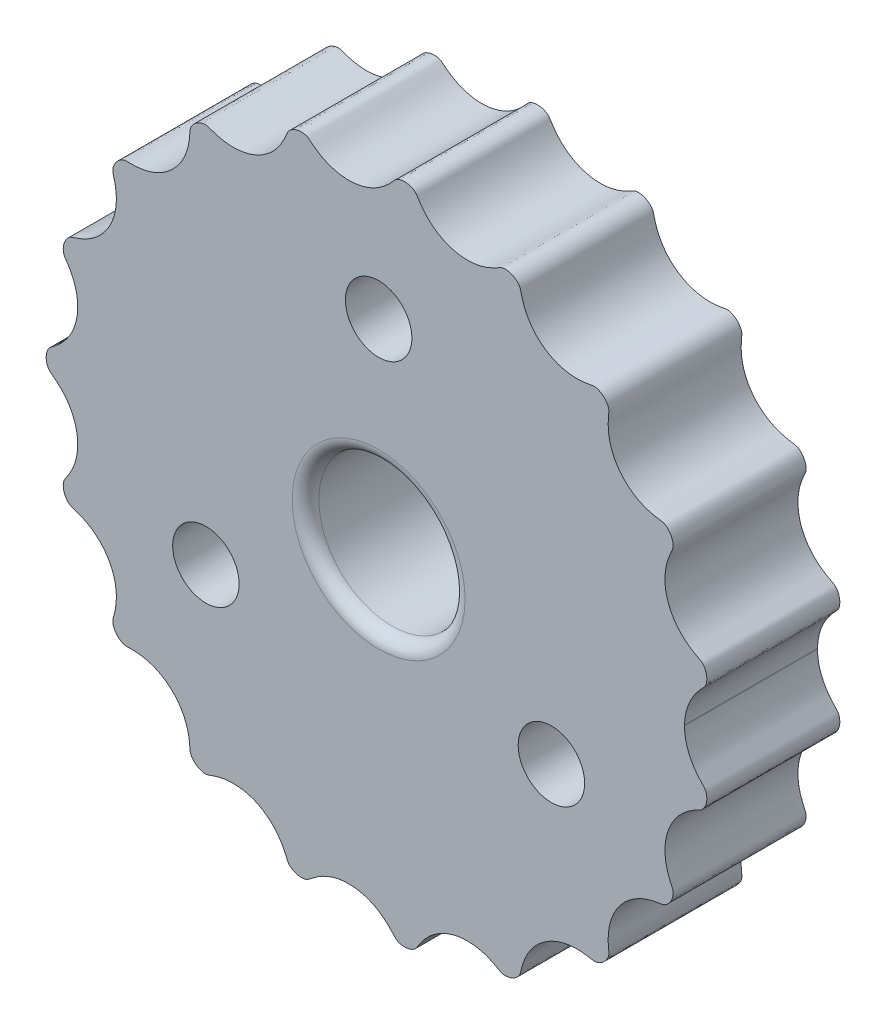
SolidWorks part; units mm, degrees
ref_plane "Ebene vorne" through (0, 0, 0) normal (0, 0, 1) x (1, 0, 0)
ref_plane "Ebene oben" through (0, 0, 0) normal (0, 1, 0) x (1, 0, 0)
ref_plane "Ebene rechts" through (0, 0, 0) normal (1, 0, 0) x (0, 0, -1)
sketch "Skizze1" plane through (0, 0, 0) normal (0, 0, 1) x (1, 0, 0)
  circle A0 centre (0, 0) radius 25
  dimension "D1" = 50
extrude "Aufsatz-Linear austragen1" add sketch "Skizze1" along normal blind 10 contours A0
sketch "Skizze3" plane through (0, 0, 10) normal (0, 0, 1) x (1, 0, 0)
  circle A0 centre (0, 25) radius 0.5
  circle A1 centre (0, 0) radius 25 construction
extrude "Schnitt-Linear austragen1" cut sketch "Skizze3" against normal up to next contours A0
pattern_circular "Kreismuster3" [suppressed] count 30 over 360 of bodies 102
sketch "Skizze9" plane through (0, 0, 10) normal (0, 0, 1) x (1, 0, 0)
  line L0 (23.0004, 0.0609) -> (23, 0)
  spline S0 degree 4 poles (21.8349, 10.4363) (21.7595, 10.2402) (21.6296, 9.8393) (21.51, 9.2154) (21.5169, 8.368) (21.6949, 7.529) (21.9996, 6.8362) (22.3616, 6.2918) (22.7278, 5.8789) (23.0126, 5.6175) (23.2743, 5.4145) (23.4929, 5.2661) (23.6607, 5.1622) (23.8217, 5.0701) (23.9556, 4.9977) (24.0711, 4.9376) (24.1728, 4.8842) (24.259, 4.8347) (24.3648, 4.7517) (24.4596, 4.6337) (24.5411, 4.4963) (24.6203, 4.3033) (24.6742, 4.0826) (24.6893, 3.8352) (24.654, 3.6047) (24.5939, 3.4337) (24.5231, 3.3149) (24.4482, 3.2274) (24.3391, 3.1139) (24.2149, 2.9815) (24.0838, 2.8346) (23.9185, 2.6346) (23.746, 2.4006) (23.5642, 2.1174) (23.3859, 1.7712) (23.2392, 1.419) (23.1381, 1.082) (23.0724, 0.8012) (23.0325, 0.5259) (23.0102, 0.3454) (22.9992, 0.0775) (22.999, -0.0665) (23.009, -0.3222) (23.0286, -0.4951) (23.0652, -0.7605) (23.1283, -1.0483) (23.2566, -1.484) (23.4559, -1.9318) (23.6809, -2.3132) (23.9099, -2.6224) (24.0743, -2.8241) (24.2067, -2.9723) (24.3336, -3.1084) (24.4467, -3.2256) (24.524, -3.3159) (24.583, -3.4156) (24.6246, -3.5208) (24.6638, -3.6686) (24.6852, -3.8609) (24.6735, -4.0869) (24.6205, -4.3068) (24.5464, -4.4848) (24.4695, -4.6144) (24.4037, -4.7024) (24.3311, -4.7784) (24.2516, -4.8395) (24.1377, -4.9039) (24.0001, -4.974) (23.846, -5.0565) (23.6352, -5.1762) (23.3933, -5.3292) (23.1212, -5.5276) (22.8316, -5.7799) (22.5655, -6.0569) (22.2617, -6.4361) (21.9548, -6.9332) (21.7249, -7.4811) (21.5829, -8.0653) (21.5273, -8.5636) (21.5216, -8.9708) (21.5541, -9.3694) (21.6218, -9.7561) (21.7087, -10.0818) (21.7995, -10.3483) (21.8842, -10.5632) (21.9558, -10.729) (22.0248, -10.8829) (22.0924, -11.0248) (22.1404, -11.1746) (22.1504, -11.3468) (22.1274, -11.5442) (22.061, -11.7619) (21.9505, -11.9788) (21.8083, -12.1674) (21.6614, -12.3022) (21.5247, -12.3914) (21.414, -12.4372) (21.3301, -12.4586) (21.2321, -12.4761) (21.1212, -12.4922) (20.9921, -12.5121) (20.8374, -12.539) (20.6763, -12.5709) (20.4655, -12.6198) (20.1205, -12.7175) (19.6539, -12.8972) (19.0899, -13.2109) (18.4957, -13.6939) (17.9798, -14.3033) (17.5818, -15.0184) (17.3599, -15.7125) (17.2758, -16.2728) (17.2579, -16.6757) (17.2603, -16.9123) (17.2683, -17.0871) (17.2802, -17.2498) (17.2921, -17.3816) (17.3037, -17.4944) (17.3123, -17.5952) (17.3148, -17.684) (17.3037, -17.7848) (17.2728, -17.8946) (17.2143, -18.0352) (17.1157, -18.1992) (16.9706, -18.3697) (16.7741, -18.5306) (16.5633, -18.6445) (16.3771, -18.7041) (16.228, -18.7183) (16.1024, -18.7064) (15.9827, -18.6847) (15.837, -18.6581) (15.664, -18.6292) (15.4825, -18.6042) (15.2505, -18.5802) (14.9676, -18.5655) (14.5429, -18.5729) (14.0693, -18.6361) (13.6043, -18.7559) (13.0666, -18.9667) (12.6278, -19.2052) (12.2149, -19.5036) (11.8389, -19.8586) (11.5583, -20.1838) (11.3157, -20.5303) (11.1115, -20.893) (10.9662, -21.2192) (10.865, -21.4994) (10.7941, -21.7329) (10.7511, -21.8937) (10.717, -22.0322) (10.6867, -22.159) (10.6596, -22.2741) (10.6135, -22.4098) (10.5273, -22.5357) (10.4274, -22.6442) (10.2911, -22.7583) (10.1265, -22.8625) (9.947, -22.94) (9.7581, -22.9885) (9.581, -23.009) (9.446, -23.0074) (9.3222, -22.9883) (9.215, -22.9494) (9.1367, -22.9105) (9.0374, -22.8556) (8.9163, -22.7867) (8.7704, -22.7082) (8.5994, -22.6214) (8.2969, -22.4821) (7.9364, -22.3488) (7.5146, -22.2402) (7.0313, -22.1759) (6.6328, -22.1607) (6.2298, -22.1836) (5.826, -22.2463) (5.4253, -22.3496) (5.032, -22.4941) (4.6565, -22.6767) (4.3023, -22.8948) (3.9755, -23.1429) (3.6777, -23.4168) (3.4441, -23.6748) (3.264, -23.904) (3.127, -24.0974) (3.026, -24.2496) (2.9434, -24.3794) (2.8771, -24.486) (2.8107, -24.5788) (2.7442, -24.6523) (2.6543, -24.7214) (2.5172, -24.8007) (2.3431, -24.8698) (2.129, -24.9172) (1.9104, -24.9257) (1.7254, -24.9049) (1.5597, -24.8634) (1.4272, -24.8123) (1.3018, -24.7374) (1.1919, -24.6254) (1.0929, -24.5126) (0.9862, -24.3949) (0.8714, -24.2728) (0.7167, -24.1173) (0.5166, -23.934) (0.1944, -23.6752) (-0.2816, -23.3734) (-0.8873, -23.1037) (-1.633, -22.9219) (-2.4119, -22.88) (-3.1838, -22.9833) (-3.829, -23.1953) (-4.2989, -23.431) (-4.6166, -23.6302) (-4.8236, -23.7746) (-4.9777, -23.8915) (-5.1193, -24.0037) (-5.2422, -24.1039) (-5.3368, -24.1704) (-5.4383, -24.2183) (-5.5428, -24.2496) (-5.6869, -24.2756) (-5.8715, -24.2822) (-6.0864, -24.2562) (-6.2931, -24.1927) (-6.4597, -24.1129) (-6.6006, -24.0204) (-6.7112, -23.9272) (-6.7966, -23.8241) (-6.8508, -23.7158) (-6.8984, -23.6058) (-6.9474, -23.4882) (-7.0086, -23.3469) (-7.0843, -23.183) (-7.1853, -22.982) (-7.3178, -22.7471) (-7.4915, -22.481) (-7.7159, -22.1922) (-7.9683, -21.919) (-8.2484, -21.6651) (-8.561, -21.4293) (-9, -21.1594) (-9.4852, -20.944) (-10.0058, -20.7949) (-10.5401, -20.7187) (-10.9664, -20.7017) (-11.386, -20.7263) (-11.7441, -20.7819) (-12.0407, -20.8508) (-12.2801, -20.9199) (-12.4645, -20.9804) (-12.619, -21.0347) (-12.7443, -21.0813) (-12.8432, -21.1127) (-12.9148, -21.1293) (-13.0155, -21.1409) (-13.1607, -21.1341) (-13.3458, -21.0947) (-13.5626, -21.0052) (-13.7727, -20.87) (-13.9463, -20.7079) (-14.067, -20.5439) (-14.1433, -20.3907) (-14.1772, -20.2506) (-14.1869, -20.1194) (-14.1984, -19.9464) (-14.2135, -19.7574) (-14.2357, -19.56) (-14.2744, -19.3096) (-14.3484, -18.9507) (-14.4988, -18.4602) (-14.7821, -17.8614) (-15.2347, -17.2299) (-15.8123, -16.6797) (-16.4915, -16.2457) (-17.1512, -15.9856) (-17.6884, -15.8653) (-18.0779, -15.8187) (-18.3444, -15.8008) (-18.5515, -15.7964) (-18.7472, -15.7971) (-18.9192, -15.8013) (-19.043, -15.798) (-19.1585, -15.7742) (-19.2639, -15.7342) (-19.3981, -15.6643) (-19.5524, -15.5524) (-19.7098, -15.3942) (-19.8355, -15.2104) (-19.9175, -15.0392) (-19.9694, -14.8748) (-19.9942, -14.7409) (-19.9941, -14.6091) (-19.9622, -14.4594) (-19.9209, -14.3132) (-19.8775, -14.147) (-19.8227, -13.9154) (-19.7703, -13.6388) (-19.7298, -13.3095) (-19.7155, -12.9316) (-19.7343, -12.5536) (-19.7865, -12.1771) (-19.8725, -11.8051) (-20.0235, -11.3478) (-20.2355, -10.9007) (-20.5061, -10.4779) (-20.8313, -10.0898) (-21.1296, -9.7984) (-21.4493, -9.5419) (-21.7859, -9.3207) (-22.0908, -9.1576) (-22.3541, -9.0395) (-22.5745, -8.9534) (-22.7489, -8.8919) (-22.9125, -8.8369) (-23.0664, -8.7897) (-23.2127, -8.7239) (-23.3488, -8.6133) (-23.48, -8.461) (-23.5959, -8.2631) (-23.6806, -8.0335) (-23.7223, -7.802) (-23.7216, -7.6015) (-23.6936, -7.4372) (-23.6459, -7.3113) (-23.587, -7.2131) (-23.5046, -7.0919) (-23.4135, -6.9559) (-23.317, -6.8055) (-23.1954, -6.601) (-23.0687, -6.3633) (-22.9383, -6.0757) (-22.7839, -5.6451) (-22.656, -5.1008) (-22.5992, -4.4221) (-22.6826, -3.6209) (-22.9272, -2.8308) (-23.2818, -2.1836) (-23.6363, -1.7308) (-23.9221, -1.4366) (-24.1011, -1.2722) (-24.239, -1.1546) (-24.372, -1.0482) (-24.4823, -0.963) (-24.578, -0.8915) (-24.662, -0.827) (-24.7323, -0.7672) (-24.8009, -0.6902) (-24.8613, -0.5932) (-24.925, -0.4573) (-24.9789, -0.2784) (-25.008, -0.0615) (-24.998, 0.1569) (-24.9616, 0.3399) (-24.9066, 0.5001) (-24.8504, 0.6156) (-24.7832, 0.7138) (-24.7061, 0.7903) (-24.6412, 0.8433) (-24.5549, 0.909) (-24.4487, 0.9887) (-24.3242, 1.0855) (-24.1833, 1.2011) (-24.0105, 1.3531) (-23.8111, 1.5469) (-23.5946, 1.788) (-23.3715, 2.0829) (-23.1734, 2.3976) (-23.0026, 2.7303) (-22.8251, 3.1685) (-22.6969, 3.6432) (-22.6277, 4.1442) (-22.6242, 4.6617) (-22.6664, 5.0951) (-22.7519, 5.5174) (-22.8777, 5.9244) (-23.0193, 6.2625) (-23.1587, 6.5356) (-23.2844, 6.7524) (-23.3883, 6.9169) (-23.4888, 7.0702) (-23.5875, 7.2108) (-23.6712, 7.3568) (-23.7142, 7.5309) (-23.7261, 7.7309) (-23.6995, 7.9535) (-23.6303, 8.1831) (-23.5263, 8.3908) (-23.4082, 8.549) (-23.2912, 8.6625) (-23.187, 8.7339) (-23.0968, 8.7758) (-22.9816, 8.8159) (-22.8484, 8.8583) (-22.6971, 8.9097) (-22.4871, 8.9859) (-22.2435, 9.0865) (-21.9662, 9.221) (-21.6596, 9.4005) (-21.366, 9.6063) (-21.0151, 9.8992) (-20.6164, 10.3191) (-20.2771, 10.8105) (-20.0144, 11.3636) (-19.8542, 11.8663) (-19.7673, 12.2789) (-19.7222, 12.6923) (-19.7169, 13.1024) (-19.7451, 13.4552) (-19.7902, 13.7494) (-19.8394, 13.9878) (-19.8839, 14.1718) (-19.9244, 14.3263) (-19.9596, 14.452) (-19.9815, 14.5509) (-19.9911, 14.6219) (-19.9935, 14.7217) (-19.9742, 14.8643) (-19.9195, 15.0445) (-19.8125, 15.2522) (-19.6794, 15.4254) (-19.5437, 15.5557) (-19.4017, 15.6607) (-19.2787, 15.7293) (-19.1504, 15.7794) (-19.0246, 15.7985) (-18.927, 15.8005) (-18.8133, 15.7991) (-18.6836, 15.7969) (-18.532, 15.7969) (-18.3106, 15.8023) (-18.0413, 15.8209) (-17.7248, 15.8628) (-17.3647, 15.941) (-16.9178, 16.0786) (-16.3974, 16.3085) (-15.8239, 16.6734) (-15.2485, 17.213) (-14.783, 17.8542) (-14.4878, 18.4827) (-14.3351, 18.9986) (-14.2627, 19.3751) (-14.2269, 19.6306) (-14.2075, 19.8274) (-14.1936, 20.0116) (-14.184, 20.1733) (-14.1697, 20.2905) (-14.1362, 20.4005) (-14.0873, 20.5015) (-14.0059, 20.6294) (-13.8804, 20.7742) (-13.7077, 20.9182) (-13.5127, 21.0276) (-13.335, 21.0939) (-13.1647, 21.1311) (-13.0232, 21.1444) (-12.8817, 21.1276) (-12.7469, 21.0817) (-12.6315, 21.0398) (-12.5001, 20.993) (-12.3519, 20.9431) (-12.1413, 20.8781) (-11.8655, 20.8075) (-11.5389, 20.7468) (-11.1616, 20.7097) (-10.7833, 20.7056) (-10.3038, 20.7432) (-9.7354, 20.8584) (-9.1818, 21.0633) (-8.6608, 21.3563) (-8.2599, 21.6542) (-7.9581, 21.9276) (-7.6875, 22.2243) (-7.4782, 22.5013) (-7.318, 22.7492) (-7.2006, 22.9556) (-7.1162, 23.1178) (-7.0401, 23.2775) (-6.9792, 23.4143) (-6.929, 23.5322) (-6.8829, 23.6417) (-6.8396, 23.7425) (-6.7732, 23.8583) (-6.6528, 23.9827) (-6.4911, 24.0996) (-6.2848, 24.1982) (-6.0489, 24.2635) (-5.8125, 24.2858) (-5.6133, 24.2679) (-5.4554, 24.2266) (-5.3475, 24.1752) (-5.2756, 24.1275) (-5.1963, 24.0667) (-5.1084, 23.9955) (-5.0052, 23.9133) (-4.8796, 23.817) (-4.7458, 23.7196) (-4.5657, 23.5973) (-4.2579, 23.4095) (-3.8065, 23.1883) (-3.1897, 22.9875) (-2.4297, 22.8812) (-1.6328, 22.9188) (-0.8411, 23.1135) (-0.1854, 23.421) (0.2799, 23.7378) (0.5861, 23.9964) (0.7572, 24.1576) (0.8795, 24.2813) (0.9904, 24.3996) (1.0788, 24.4971) (1.1534, 24.5815) (1.2215, 24.6556) (1.2849, 24.7171) (1.366, 24.7765) (1.4665, 24.8274) (1.6073, 24.879) (1.7912, 24.9173) (2.0109, 24.9275) (2.2284, 24.8982) (2.4076, 24.8457) (2.5635, 24.7759) (2.6787, 24.7064) (2.7776, 24.6216) (2.853, 24.522) (2.9089, 24.4353) (2.9741, 24.3312) (3.0513, 24.2111) (3.1673, 24.0378) (3.3314, 23.8136) (3.5412, 23.5623) (3.803, 23.2967) (4.0867, 23.0548) (4.3911, 22.8375) (4.7145, 22.6472) (5.1434, 22.4443) (5.6099, 22.2897) (6.1032, 22.1928) (6.6136, 22.1597) (7.04, 22.1755) (7.456, 22.233) (7.8578, 22.329) (8.1935, 22.443) (8.4659, 22.558) (8.6842, 22.6634) (8.8514, 22.7516) (9.0063, 22.8365) (9.1484, 22.9196) (9.3008, 22.9869) (9.4518, 23.0083) (9.5997, 23.0081) (9.7768, 22.9846) (9.9657, 22.9334) (10.1449, 22.8528) (10.3091, 22.7455) (10.4441, 22.6278) (10.5341, 22.5264) (10.6032, 22.4212) (10.6459, 22.3149) (10.6698, 22.2304) (10.6965, 22.1196) (10.7284, 21.9833) (10.7696, 21.8219) (10.8224, 21.6365) (10.926, 21.3181) (11.074, 20.9612) (11.2824, 20.576) (11.5658, 20.1761) (11.8273, 19.8724) (12.1194, 19.5924) (12.4404, 19.3397) (12.8767, 19.0608) (13.3474, 18.8414) (13.8414, 18.6865) (14.3466, 18.5977) (14.6978, 18.5693) (14.9983, 18.5678) (15.2424, 18.5806) (15.4319, 18.5983) (15.6163, 18.622) (15.7956, 18.651) (15.9629, 18.6804) (16.1188, 18.7114) (16.2634, 18.7186) (16.3919, 18.6957) (16.5434, 18.6484) (16.7128, 18.5663) (16.8932, 18.44) (17.0477, 18.2836) (17.1576, 18.1324) (17.2387, 17.9815) (17.2904, 17.8485) (17.3189, 17.7045) (17.3093, 17.5471) (17.2934, 17.3968) (17.2791, 17.2377) (17.2672, 17.07) (17.2581, 16.8499) (17.2594, 16.5774) (17.2886, 16.1632) (17.3914, 15.6061) (17.6071, 14.9758) (17.9828, 14.3047) (18.4824, 13.7066) (19.0811, 13.2137) (19.6713, 12.887) (20.16, 12.7034) (20.5195, 12.6059) (20.7644, 12.5521) (20.9536, 12.5182) (21.1309, 12.4903) (21.2868, 12.4679) (21.399, 12.4432) (21.5025, 12.4008) (21.5963, 12.345) (21.7134, 12.2561) (21.8437, 12.1238) (21.9702, 11.9469) (22.0634, 11.7504) (22.117, 11.5726) (22.1436, 11.4054) (22.149, 11.2598) (22.129, 11.1267) (22.0845, 11.0132) (22.035, 10.903) (21.9816, 10.7867) (21.919, 10.6454) (21.8499, 10.4782) (21.7706, 10.2666) (21.6878, 10.0086) (21.6103, 9.6986) (21.5509, 9.3355) (21.5224, 8.9626) (21.5272, 8.5827) (21.5787, 8.0866) (21.6972, 7.5846) (21.8865, 7.0905) (22.1457, 6.6199) (22.3909, 6.2662) (22.6666, 5.9438) (22.9679, 5.6541) (23.2503, 5.43) (23.5008, 5.2597) (23.7129, 5.1314) (23.8814, 5.0373) (24.0251, 4.9609) (24.1437, 4.9005) (24.2332, 4.8492) (24.2935, 4.8079) (24.37, 4.7415) (24.4633, 4.6297) (24.5599, 4.466) (24.6407, 4.2447) (24.683, 3.9972) (24.6804, 3.7586) (24.6403, 3.558) (24.5776, 3.3979) (24.4956, 3.2786) (24.4048, 3.1827) (24.2851, 3.0565) (24.1558, 2.9165) (24.0253, 2.7659) (23.8669, 2.5657) (23.6527, 2.2673) (23.442, 1.9019) (23.2546, 1.4742) (23.132, 1.0608) (23.0706, 0.7861) (23.0335, 0.5349) (23.0132, 0.3678) (23.0003, 0.1223) (22.9986, -0.0189) (23.0056, -0.2852) (23.0253, -0.4661) (23.0615, -0.7427) (23.1239, -1.029) (23.2494, -1.4644) (23.4447, -1.9094) (23.6681, -2.2941) (23.8991, -2.6086) (24.0657, -2.8141) (24.1984, -2.9632) (24.3246, -3.0987) (24.4356, -3.2143) (24.5132, -3.3018) (24.5877, -3.4196) (24.6374, -3.5547) (24.6701, -3.7073) (24.6838, -3.9154) (24.6644, -4.1417) (24.6, -4.381) (24.4916, -4.5912) (24.3759, -4.7394) (24.2736, -4.8247) (24.1898, -4.8749) (24.0901, -4.9279) (23.9765, -4.9865) (23.845, -5.0574) (23.6862, -5.1471) (23.5208, -5.2483) (23.3047, -5.3926) (23.0455, -5.59) (22.7627, -5.8442) (22.3976, -6.2458) (22.0314, -6.7792) (21.7172, -7.4627) (21.5252, -8.2962) (21.504, -9.1452) (21.6139, -9.7724) (21.7382, -10.176) (21.8113, -10.3736) knots 0 0 0 0 0 0.004237 0.008483 0.012729 0.016973 0.021413 0.023634 0.025855 0.02808 0.029193 0.030306 0.031182 0.032058 0.032934 0.033372 0.03381 0.034372 0.034934 0.036073 0.036831 0.037589 0.039124 0.04064 0.041779 0.042264 0.042749 0.043421 0.044093 0.045438 0.046411 0.047385 0.049332 0.051278 0.053223 0.055168 0.057112 0.0582 0.059287 0.060374 0.061462 0.062481 0.063501 0.064521 0.06554 0.067576 0.069612 0.073551 0.075471 0.07643 0.07739 0.078785 0.079482 0.08018 0.080676 0.081172 0.081811 0.082451 0.083753 0.085056 0.086348 0.086986 0.087623 0.08809 0.088558 0.089098 0.089639 0.090721 0.091672 0.092623 0.094526 0.09649 0.098454 0.100357 0.102259 0.106274 0.110193 0.112266 0.114339 0.116366 0.118392 0.120318 0.122244 0.123155 0.124065 0.124975 0.125886 0.126558 0.12723 0.128129 0.12933 0.130553 0.131784 0.13302 0.134061 0.134556 0.135052 0.135429 0.135805 0.136559 0.137312 0.138066 0.138968 0.13987 0.141675 0.145292 0.149024 0.152819 0.157032 0.161293 0.165414 0.167417 0.168419 0.16942 0.170182 0.170945 0.171707 0.172088 0.17247 0.172983 0.173496 0.174127 0.174758 0.176047 0.177335 0.178622 0.179842 0.180858 0.181239 0.181621 0.182383 0.183306 0.18423 0.185154 0.186077 0.188008 0.189939 0.193707 0.195683 0.19766 0.201566 0.203743 0.205919 0.208066 0.210213 0.212256 0.214298 0.215257 0.216216 0.217175 0.217654 0.218133 0.218845 0.219557 0.220527 0.221173 0.221818 0.22313 0.224442 0.22509 0.225738 0.226717 0.227156 0.227596 0.228035 0.228475 0.229441 0.230408 0.231375 0.232341 0.236155 0.238143 0.24013 0.242157 0.244184 0.24627 0.248355 0.250487 0.252618 0.254674 0.25673 0.258747 0.260763 0.261683 0.262604 0.263524 0.264444 0.264789 0.265133 0.265821 0.26644 0.267059 0.26832 0.269582 0.270836 0.271447 0.272058 0.273021 0.273691 0.274361 0.275205 0.27605 0.276894 0.277739 0.279628 0.281518 0.285219 0.28907 0.292926 0.296908 0.300855 0.304679 0.306545 0.307478 0.308411 0.309767 0.310445 0.311123 0.311607 0.31209 0.312702 0.313313 0.314555 0.3158 0.31704 0.317653 0.318265 0.319194 0.319946 0.320323 0.320699 0.321608 0.322518 0.323427 0.324337 0.326144 0.327952 0.329828 0.331704 0.333634 0.335564 0.337712 0.342077 0.344294 0.346435 0.348576 0.350665 0.352755 0.353733 0.35471 0.355688 0.356666 0.357036 0.357406 0.357777 0.358147 0.359078 0.360318 0.361577 0.362842 0.364095 0.365072 0.365667 0.366263 0.366989 0.367716 0.369169 0.370082 0.370996 0.372823 0.376553 0.380398 0.384283 0.388402 0.39254 0.396544 0.398494 0.399468 0.400443 0.401928 0.402671 0.403414 0.403914 0.404414 0.405044 0.405674 0.406958 0.408242 0.409517 0.410142 0.410767 0.411715 0.412247 0.41278 0.413844 0.414778 0.415711 0.417578 0.419518 0.421458 0.423328 0.425198 0.427172 0.429146 0.433023 0.435141 0.437259 0.439338 0.441417 0.443393 0.445369 0.446301 0.447232 0.448164 0.449096 0.449784 0.450473 0.451382 0.452594 0.453825 0.455064 0.456299 0.457303 0.457852 0.458401 0.459003 0.459604 0.460806 0.461705 0.462604 0.464401 0.466234 0.468066 0.471816 0.475642 0.479892 0.484207 0.488376 0.490424 0.491448 0.492472 0.493275 0.494078 0.494881 0.495283 0.495684 0.496212 0.496739 0.497357 0.497975 0.499232 0.500491 0.501743 0.502362 0.50298 0.503902 0.504323 0.504745 0.505167 0.505588 0.506507 0.507426 0.508345 0.509264 0.511146 0.513029 0.51487 0.51671 0.518635 0.520559 0.52439 0.526593 0.528795 0.530975 0.533155 0.535264 0.537372 0.538353 0.539334 0.540315 0.541296 0.542048 0.5428 0.543686 0.54487 0.546076 0.547289 0.548505 0.549524 0.55004 0.550557 0.551041 0.551525 0.552494 0.553378 0.554262 0.556029 0.557808 0.559586 0.561418 0.563249 0.567013 0.571226 0.573386 0.575547 0.57763 0.579713 0.581758 0.583803 0.584757 0.585711 0.586665 0.587619 0.587981 0.588342 0.588703 0.589064 0.589991 0.591226 0.592482 0.593745 0.594375 0.595005 0.596035 0.596581 0.597126 0.597563 0.597999 0.598872 0.599744 0.600617 0.602465 0.604312 0.606175 0.608037 0.611883 0.615748 0.619804 0.623847 0.62776 0.629667 0.63062 0.631574 0.63296 0.633653 0.634347 0.63484 0.635333 0.635965 0.636598 0.63789 0.639181 0.640471 0.641084 0.641696 0.642695 0.643315 0.643934 0.644554 0.645174 0.64613 0.647085 0.648997 0.65091 0.652822 0.654719 0.656616 0.660595 0.664476 0.666551 0.668626 0.67065 0.672674 0.674636 0.675617 0.676598 0.67746 0.678322 0.679184 0.679615 0.680046 0.680718 0.68139 0.682294 0.683501 0.68473 0.685967 0.68721 0.688256 0.688745 0.689234 0.689614 0.689994 0.690755 0.691516 0.692276 0.693184 0.694091 0.695906 0.699541 0.703294 0.707104 0.711296 0.715529 0.719623 0.721614 0.722609 0.723605 0.724363 0.72512 0.725878 0.726257 0.726636 0.727147 0.727657 0.728278 0.728898 0.730163 0.731429 0.732687 0.7333 0.733914 0.734868 0.735387 0.735906 0.736425 0.736945 0.737866 0.738787 0.740628 0.742544 0.74446 0.746298 0.748136 0.750076 0.752015 0.75585 0.758014 0.760177 0.762308 0.764439 0.766466 0.768494 0.769446 0.770399 0.771352 0.772304 0.773011 0.773717 0.774692 0.775341 0.77599 0.777308 0.778627 0.779278 0.77993 0.780912 0.781353 0.781795 0.782237 0.782678 0.78365 0.784622 0.785593 0.786565 0.790399 0.792398 0.794396 0.796432 0.798468 0.800544 0.802619 0.806855 0.808898 0.810941 0.812947 0.81395 0.814953 0.815868 0.816783 0.817698 0.818613 0.819297 0.819981 0.820603 0.821225 0.822492 0.82376 0.825019 0.825633 0.826247 0.827208 0.827886 0.828563 0.829411 0.830258 0.831106 0.831953 0.833852 0.83575 0.83947 0.843342 0.847212 0.851172 0.85509 0.858888 0.860742 0.861669 0.862595 0.863943 0.864616 0.86529 0.86577 0.866251 0.866866 0.86748 0.868728 0.86998 0.871226 0.871843 0.872459 0.87339 0.87415 0.87453 0.874909 0.875821 0.876733 0.877645 0.878557 0.880376 0.882194 0.884081 0.885968 0.887906 0.889845 0.894123 0.896327 0.898531 0.900659 0.902786 0.904866 0.906945 0.907918 0.90889 0.909862 0.910835 0.911203 0.911571 0.911939 0.912307 0.913243 0.914489 0.915755 0.917025 0.918283 0.919266 0.919863 0.920461 0.92119 0.921919 0.923377 0.924296 0.925215 0.927054 0.930802 0.932735 0.934668 0.935643 0.936618 0.937593 0.938568 0.939657 0.940745 0.941834 0.942922 0.944896 0.946869 0.950817 0.952789 0.953776 0.954762 0.956135 0.956821 0.957507 0.957996 0.958485 0.959623 0.960381 0.961139 0.962673 0.964189 0.965328 0.965881 0.966433 0.966863 0.967294 0.968154 0.969015 0.969875 0.970969 0.972064 0.974253 0.976438 0.978623 0.98299 0.987244 0.991499 0.995751 1 1 1 1 1 construction
  spline S1 degree 4 poles (23, 0) (23, -0.0443) (23.0016, -0.1335) (23.009, -0.3222) (23.0286, -0.4951) (23.0652, -0.7605) (23.1283, -1.0483) (23.2566, -1.484) (23.4559, -1.9318) (23.6809, -2.3132) (23.9099, -2.6224) (24.0743, -2.8241) (24.2067, -2.9723) (24.3336, -3.1084) (24.4467, -3.2256) (24.524, -3.3159) (24.583, -3.4156) (24.6246, -3.5208) (24.6638, -3.6686) (24.6852, -3.8609) (24.6735, -4.0869) (24.6205, -4.3068) (24.5464, -4.4848) (24.4695, -4.6144) (24.4037, -4.7024) (24.3311, -4.7784) (24.2516, -4.8395) (24.1377, -4.9039) (24.0001, -4.974) (23.846, -5.0565) (23.6352, -5.1762) (23.3933, -5.3292) (23.1212, -5.5276) (22.8316, -5.7799) (22.5655, -6.0569) (22.2617, -6.4361) (21.9548, -6.9332) (21.7249, -7.4811) (21.5829, -8.0653) (21.5273, -8.5636) (21.5216, -8.9708) (21.5541, -9.3694) (21.6218, -9.7561) (21.7087, -10.0818) (21.7995, -10.3483) (21.8842, -10.5632) (21.9558, -10.729) (22.0248, -10.8829) (22.0924, -11.0248) (22.1404, -11.1746) (22.1504, -11.3468) (22.1274, -11.5442) (22.061, -11.7619) (21.9505, -11.9788) (21.8083, -12.1674) (21.6614, -12.3022) (21.5247, -12.3914) (21.414, -12.4372) (21.3301, -12.4586) (21.2321, -12.4761) (21.1212, -12.4922) (20.9921, -12.5121) (20.8374, -12.539) (20.6763, -12.5709) (20.4655, -12.6198) (20.1205, -12.7175) (19.6539, -12.8972) (19.0899, -13.2109) (18.4957, -13.6939) (17.9798, -14.3033) (17.5818, -15.0184) (17.3599, -15.7125) (17.2758, -16.2728) (17.2579, -16.6757) (17.2603, -16.9123) (17.2683, -17.0871) (17.2802, -17.2498) (17.2921, -17.3816) (17.3037, -17.4944) (17.3123, -17.5952) (17.3148, -17.684) (17.3037, -17.7848) (17.2728, -17.8946) (17.2143, -18.0352) (17.1157, -18.1992) (16.9706, -18.3697) (16.7741, -18.5306) (16.5633, -18.6445) (16.3771, -18.7041) (16.228, -18.7183) (16.1024, -18.7064) (15.9827, -18.6847) (15.837, -18.6581) (15.664, -18.6292) (15.4825, -18.6042) (15.2505, -18.5802) (14.9676, -18.5655) (14.5429, -18.5729) (14.0693, -18.6361) (13.6043, -18.7559) (13.0666, -18.9667) (12.6278, -19.2052) (12.2149, -19.5036) (11.8389, -19.8586) (11.5583, -20.1838) (11.3157, -20.5303) (11.1115, -20.893) (10.9662, -21.2192) (10.865, -21.4994) (10.7941, -21.7329) (10.7511, -21.8937) (10.717, -22.0322) (10.6867, -22.159) (10.6596, -22.2741) (10.6135, -22.4098) (10.5273, -22.5357) (10.4274, -22.6442) (10.2911, -22.7583) (10.1265, -22.8625) (9.947, -22.94) (9.7581, -22.9885) (9.581, -23.009) (9.446, -23.0074) (9.3222, -22.9883) (9.215, -22.9494) (9.1367, -22.9105) (9.0374, -22.8556) (8.9163, -22.7867) (8.7704, -22.7082) (8.5994, -22.6214) (8.2969, -22.4821) (7.9364, -22.3488) (7.5146, -22.2402) (7.0313, -22.1759) (6.6328, -22.1607) (6.2298, -22.1836) (5.826, -22.2463) (5.4253, -22.3496) (5.032, -22.4941) (4.6565, -22.6767) (4.3023, -22.8948) (3.9755, -23.1429) (3.6777, -23.4168) (3.4441, -23.6748) (3.264, -23.904) (3.127, -24.0974) (3.026, -24.2496) (2.9434, -24.3794) (2.8771, -24.486) (2.8107, -24.5788) (2.7442, -24.6523) (2.6543, -24.7214) (2.5172, -24.8007) (2.3431, -24.8698) (2.129, -24.9172) (1.9104, -24.9257) (1.7254, -24.9049) (1.5597, -24.8634) (1.4272, -24.8123) (1.3018, -24.7374) (1.1919, -24.6254) (1.0929, -24.5126) (0.9862, -24.3949) (0.8714, -24.2728) (0.7167, -24.1173) (0.5166, -23.934) (0.1944, -23.6752) (-0.2816, -23.3734) (-0.8873, -23.1037) (-1.633, -22.9219) (-2.4119, -22.88) (-3.1838, -22.9833) (-3.829, -23.1953) (-4.2989, -23.431) (-4.6166, -23.6302) (-4.8236, -23.7746) (-4.9777, -23.8915) (-5.1193, -24.0037) (-5.2422, -24.1039) (-5.3368, -24.1704) (-5.4383, -24.2183) (-5.5428, -24.2496) (-5.6869, -24.2756) (-5.8715, -24.2822) (-6.0864, -24.2562) (-6.2931, -24.1927) (-6.4597, -24.1129) (-6.6006, -24.0204) (-6.7112, -23.9272) (-6.7966, -23.8241) (-6.8508, -23.7158) (-6.8984, -23.6058) (-6.9474, -23.4882) (-7.0086, -23.3469) (-7.0843, -23.183) (-7.1853, -22.982) (-7.3178, -22.7471) (-7.4915, -22.481) (-7.7159, -22.1922) (-7.9683, -21.919) (-8.2484, -21.6651) (-8.561, -21.4293) (-9, -21.1594) (-9.4852, -20.944) (-10.0058, -20.7949) (-10.5401, -20.7187) (-10.9664, -20.7017) (-11.386, -20.7263) (-11.7441, -20.7819) (-12.0407, -20.8508) (-12.2801, -20.9199) (-12.4645, -20.9804) (-12.619, -21.0347) (-12.7443, -21.0813) (-12.8432, -21.1127) (-12.9148, -21.1293) (-13.0155, -21.1409) (-13.1607, -21.1341) (-13.3458, -21.0947) (-13.5626, -21.0052) (-13.7727, -20.87) (-13.9463, -20.7079) (-14.067, -20.5439) (-14.1433, -20.3907) (-14.1772, -20.2506) (-14.1869, -20.1194) (-14.1984, -19.9464) (-14.2135, -19.7574) (-14.2357, -19.56) (-14.2744, -19.3096) (-14.3484, -18.9507) (-14.4988, -18.4602) (-14.7821, -17.8614) (-15.2347, -17.2299) (-15.8123, -16.6797) (-16.4915, -16.2457) (-17.1512, -15.9856) (-17.6884, -15.8653) (-18.0779, -15.8187) (-18.3444, -15.8008) (-18.5515, -15.7964) (-18.7472, -15.7971) (-18.9192, -15.8013) (-19.043, -15.798) (-19.1585, -15.7742) (-19.2639, -15.7342) (-19.3981, -15.6643) (-19.5524, -15.5524) (-19.7098, -15.3942) (-19.8355, -15.2104) (-19.9175, -15.0392) (-19.9694, -14.8748) (-19.9942, -14.7409) (-19.9941, -14.6091) (-19.9622, -14.4594) (-19.9209, -14.3132) (-19.8775, -14.147) (-19.8227, -13.9154) (-19.7703, -13.6388) (-19.7298, -13.3095) (-19.7155, -12.9316) (-19.7343, -12.5536) (-19.7865, -12.1771) (-19.8725, -11.8051) (-20.0235, -11.3478) (-20.2355, -10.9007) (-20.5061, -10.4779) (-20.8313, -10.0898) (-21.1296, -9.7984) (-21.4493, -9.5419) (-21.7859, -9.3207) (-22.0908, -9.1576) (-22.3541, -9.0395) (-22.5745, -8.9534) (-22.7489, -8.8919) (-22.9125, -8.8369) (-23.0664, -8.7897) (-23.2127, -8.7239) (-23.3488, -8.6133) (-23.48, -8.461) (-23.5959, -8.2631) (-23.6806, -8.0335) (-23.7223, -7.802) (-23.7216, -7.6015) (-23.6936, -7.4372) (-23.6459, -7.3113) (-23.587, -7.2131) (-23.5046, -7.0919) (-23.4135, -6.9559) (-23.317, -6.8055) (-23.1954, -6.601) (-23.0687, -6.3633) (-22.9383, -6.0757) (-22.7839, -5.6451) (-22.656, -5.1008) (-22.5992, -4.4221) (-22.6826, -3.6209) (-22.9272, -2.8308) (-23.2818, -2.1836) (-23.6363, -1.7308) (-23.9221, -1.4366) (-24.1011, -1.2722) (-24.239, -1.1546) (-24.372, -1.0482) (-24.4823, -0.963) (-24.578, -0.8915) (-24.662, -0.827) (-24.7323, -0.7672) (-24.8009, -0.6902) (-24.8613, -0.5932) (-24.925, -0.4573) (-24.9789, -0.2784) (-25.008, -0.0615) (-24.998, 0.1569) (-24.9616, 0.3399) (-24.9066, 0.5001) (-24.8504, 0.6156) (-24.7832, 0.7138) (-24.7061, 0.7903) (-24.6412, 0.8433) (-24.5549, 0.909) (-24.4487, 0.9887) (-24.3242, 1.0855) (-24.1833, 1.2011) (-24.0105, 1.3531) (-23.8111, 1.5469) (-23.5946, 1.788) (-23.3715, 2.0829) (-23.1734, 2.3976) (-23.0026, 2.7303) (-22.8251, 3.1685) (-22.6969, 3.6432) (-22.6277, 4.1442) (-22.6242, 4.6617) (-22.6664, 5.0951) (-22.7519, 5.5174) (-22.8777, 5.9244) (-23.0193, 6.2625) (-23.1587, 6.5356) (-23.2844, 6.7524) (-23.3883, 6.9169) (-23.4888, 7.0702) (-23.5875, 7.2108) (-23.6712, 7.3568) (-23.7142, 7.5309) (-23.7261, 7.7309) (-23.6995, 7.9535) (-23.6303, 8.1831) (-23.5263, 8.3908) (-23.4082, 8.549) (-23.2912, 8.6625) (-23.187, 8.7339) (-23.0968, 8.7758) (-22.9816, 8.8159) (-22.8484, 8.8583) (-22.6971, 8.9097) (-22.4871, 8.9859) (-22.2435, 9.0865) (-21.9662, 9.221) (-21.6596, 9.4005) (-21.366, 9.6063) (-21.0151, 9.8992) (-20.6164, 10.3191) (-20.2771, 10.8105) (-20.0144, 11.3636) (-19.8542, 11.8663) (-19.7673, 12.2789) (-19.7222, 12.6923) (-19.7169, 13.1024) (-19.7451, 13.4552) (-19.7902, 13.7494) (-19.8394, 13.9878) (-19.8839, 14.1718) (-19.9244, 14.3263) (-19.9596, 14.452) (-19.9815, 14.5509) (-19.9911, 14.6219) (-19.9935, 14.7217) (-19.9742, 14.8643) (-19.9195, 15.0445) (-19.8125, 15.2522) (-19.6794, 15.4254) (-19.5437, 15.5557) (-19.4017, 15.6607) (-19.2787, 15.7293) (-19.1504, 15.7794) (-19.0246, 15.7985) (-18.927, 15.8005) (-18.8133, 15.7991) (-18.6836, 15.7969) (-18.532, 15.7969) (-18.3106, 15.8023) (-18.0413, 15.8209) (-17.7248, 15.8628) (-17.3647, 15.941) (-16.9178, 16.0786) (-16.3974, 16.3085) (-15.8239, 16.6734) (-15.2485, 17.213) (-14.783, 17.8542) (-14.4878, 18.4827) (-14.3351, 18.9986) (-14.2627, 19.3751) (-14.2269, 19.6306) (-14.2075, 19.8274) (-14.1936, 20.0116) (-14.184, 20.1733) (-14.1697, 20.2905) (-14.1362, 20.4005) (-14.0873, 20.5015) (-14.0059, 20.6294) (-13.8804, 20.7742) (-13.7077, 20.9182) (-13.5127, 21.0276) (-13.335, 21.0939) (-13.1647, 21.1311) (-13.0232, 21.1444) (-12.8817, 21.1276) (-12.7469, 21.0817) (-12.6315, 21.0398) (-12.5001, 20.993) (-12.3519, 20.9431) (-12.1413, 20.8781) (-11.8655, 20.8075) (-11.5389, 20.7468) (-11.1616, 20.7097) (-10.7833, 20.7056) (-10.3038, 20.7432) (-9.7354, 20.8584) (-9.1818, 21.0633) (-8.6608, 21.3563) (-8.2599, 21.6542) (-7.9581, 21.9276) (-7.6875, 22.2243) (-7.4782, 22.5013) (-7.318, 22.7492) (-7.2006, 22.9556) (-7.1162, 23.1178) (-7.0401, 23.2775) (-6.9792, 23.4143) (-6.929, 23.5322) (-6.8829, 23.6417) (-6.8396, 23.7425) (-6.7732, 23.8583) (-6.6528, 23.9827) (-6.4911, 24.0996) (-6.2848, 24.1982) (-6.0489, 24.2635) (-5.8125, 24.2858) (-5.6133, 24.2679) (-5.4554, 24.2266) (-5.3475, 24.1752) (-5.2756, 24.1275) (-5.1963, 24.0667) (-5.1084, 23.9955) (-5.0052, 23.9133) (-4.8796, 23.817) (-4.7458, 23.7196) (-4.5657, 23.5973) (-4.2579, 23.4095) (-3.8065, 23.1883) (-3.1897, 22.9875) (-2.4297, 22.8812) (-1.6328, 22.9188) (-0.8411, 23.1135) (-0.1854, 23.421) (0.2799, 23.7378) (0.5861, 23.9964) (0.7572, 24.1576) (0.8795, 24.2813) (0.9904, 24.3996) (1.0788, 24.4971) (1.1534, 24.5815) (1.2215, 24.6556) (1.2849, 24.7171) (1.366, 24.7765) (1.4665, 24.8274) (1.6073, 24.879) (1.7912, 24.9173) (2.0109, 24.9275) (2.2284, 24.8982) (2.4076, 24.8457) (2.5635, 24.7759) (2.6787, 24.7064) (2.7776, 24.6216) (2.853, 24.522) (2.9089, 24.4353) (2.9741, 24.3312) (3.0513, 24.2111) (3.1673, 24.0378) (3.3314, 23.8136) (3.5412, 23.5623) (3.803, 23.2967) (4.0867, 23.0548) (4.3911, 22.8375) (4.7145, 22.6472) (5.1434, 22.4443) (5.6099, 22.2897) (6.1032, 22.1928) (6.6136, 22.1597) (7.04, 22.1755) (7.456, 22.233) (7.8578, 22.329) (8.1935, 22.443) (8.4659, 22.558) (8.6842, 22.6634) (8.8514, 22.7516) (9.0063, 22.8365) (9.1484, 22.9196) (9.3008, 22.9869) (9.4518, 23.0083) (9.5997, 23.0081) (9.7768, 22.9846) (9.9657, 22.9334) (10.1449, 22.8528) (10.3091, 22.7455) (10.4441, 22.6278) (10.5341, 22.5264) (10.6032, 22.4212) (10.6459, 22.3149) (10.6698, 22.2304) (10.6965, 22.1196) (10.7284, 21.9833) (10.7696, 21.8219) (10.8224, 21.6365) (10.926, 21.3181) (11.074, 20.9612) (11.2824, 20.576) (11.5658, 20.1761) (11.8273, 19.8724) (12.1194, 19.5924) (12.4404, 19.3397) (12.8767, 19.0608) (13.3474, 18.8414) (13.8414, 18.6865) (14.3466, 18.5977) (14.6978, 18.5693) (14.9983, 18.5678) (15.2424, 18.5806) (15.4319, 18.5983) (15.6163, 18.622) (15.7956, 18.651) (15.9629, 18.6804) (16.1188, 18.7114) (16.2634, 18.7186) (16.3919, 18.6957) (16.5434, 18.6484) (16.7128, 18.5663) (16.8932, 18.44) (17.0477, 18.2836) (17.1576, 18.1324) (17.2387, 17.9815) (17.2904, 17.8485) (17.3189, 17.7045) (17.3093, 17.5471) (17.2934, 17.3968) (17.2791, 17.2377) (17.2672, 17.07) (17.2581, 16.8499) (17.2594, 16.5774) (17.2886, 16.1632) (17.3914, 15.6061) (17.6071, 14.9758) (17.9828, 14.3047) (18.4824, 13.7066) (19.0811, 13.2137) (19.6713, 12.887) (20.16, 12.7034) (20.5195, 12.6059) (20.7644, 12.5521) (20.9536, 12.5182) (21.1309, 12.4903) (21.2868, 12.4679) (21.399, 12.4432) (21.5025, 12.4008) (21.5963, 12.345) (21.7134, 12.2561) (21.8437, 12.1238) (21.9702, 11.9469) (22.0634, 11.7504) (22.117, 11.5726) (22.1436, 11.4054) (22.149, 11.2598) (22.129, 11.1267) (22.0845, 11.0132) (22.035, 10.903) (21.9816, 10.7867) (21.919, 10.6454) (21.8499, 10.4782) (21.7706, 10.2666) (21.6878, 10.0086) (21.6103, 9.6986) (21.5509, 9.3355) (21.5224, 8.9626) (21.5272, 8.5827) (21.5787, 8.0866) (21.6972, 7.5846) (21.8865, 7.0905) (22.1457, 6.6199) (22.3909, 6.2662) (22.6666, 5.9438) (22.9679, 5.6541) (23.2503, 5.43) (23.5008, 5.2597) (23.7129, 5.1314) (23.8814, 5.0373) (24.0251, 4.9609) (24.1437, 4.9005) (24.2332, 4.8492) (24.2935, 4.8079) (24.37, 4.7415) (24.4633, 4.6297) (24.5599, 4.466) (24.6407, 4.2447) (24.683, 3.9972) (24.6804, 3.7586) (24.6403, 3.558) (24.5776, 3.3979) (24.4956, 3.2786) (24.4048, 3.1827) (24.2851, 3.0565) (24.1558, 2.9165) (24.0253, 2.7659) (23.8669, 2.5657) (23.6527, 2.2673) (23.442, 1.9019) (23.2546, 1.4742) (23.132, 1.0608) (23.0706, 0.7861) (23.0335, 0.5349) (23.0132, 0.3678) (23.0038, 0.1889) (23.0011, 0.1033) (23.0004, 0.0609) knots 0.061462 0.061462 0.061462 0.061462 0.061462 0.062481 0.063501 0.064521 0.06554 0.067576 0.069612 0.073551 0.075471 0.07643 0.07739 0.078785 0.079482 0.08018 0.080676 0.081172 0.081811 0.082451 0.083753 0.085056 0.086348 0.086986 0.087623 0.08809 0.088558 0.089098 0.089639 0.090721 0.091672 0.092623 0.094526 0.09649 0.098454 0.100357 0.102259 0.106274 0.110193 0.112266 0.114339 0.116366 0.118392 0.120318 0.122244 0.123155 0.124065 0.124975 0.125886 0.126558 0.12723 0.128129 0.12933 0.130553 0.131784 0.13302 0.134061 0.134556 0.135052 0.135429 0.135805 0.136559 0.137312 0.138066 0.138968 0.13987 0.141675 0.145292 0.149024 0.152819 0.157032 0.161293 0.165414 0.167417 0.168419 0.16942 0.170182 0.170945 0.171707 0.172088 0.17247 0.172983 0.173496 0.174127 0.174758 0.176047 0.177335 0.178622 0.179842 0.180858 0.181239 0.181621 0.182383 0.183306 0.18423 0.185154 0.186077 0.188008 0.189939 0.193707 0.195683 0.19766 0.201566 0.203743 0.205919 0.208066 0.210213 0.212256 0.214298 0.215257 0.216216 0.217175 0.217654 0.218133 0.218845 0.219557 0.220527 0.221173 0.221818 0.22313 0.224442 0.22509 0.225738 0.226717 0.227156 0.227596 0.228035 0.228475 0.229441 0.230408 0.231375 0.232341 0.236155 0.238143 0.24013 0.242157 0.244184 0.24627 0.248355 0.250487 0.252618 0.254674 0.25673 0.258747 0.260763 0.261683 0.262604 0.263524 0.264444 0.264789 0.265133 0.265821 0.26644 0.267059 0.26832 0.269582 0.270836 0.271447 0.272058 0.273021 0.273691 0.274361 0.275205 0.27605 0.276894 0.277739 0.279628 0.281518 0.285219 0.28907 0.292926 0.296908 0.300855 0.304679 0.306545 0.307478 0.308411 0.309767 0.310445 0.311123 0.311607 0.31209 0.312702 0.313313 0.314555 0.3158 0.31704 0.317653 0.318265 0.319194 0.319946 0.320323 0.320699 0.321608 0.322518 0.323427 0.324337 0.326144 0.327952 0.329828 0.331704 0.333634 0.335564 0.337712 0.342077 0.344294 0.346435 0.348576 0.350665 0.352755 0.353733 0.35471 0.355688 0.356666 0.357036 0.357406 0.357777 0.358147 0.359078 0.360318 0.361577 0.362842 0.364095 0.365072 0.365667 0.366263 0.366989 0.367716 0.369169 0.370082 0.370996 0.372823 0.376553 0.380398 0.384283 0.388402 0.39254 0.396544 0.398494 0.399468 0.400443 0.401928 0.402671 0.403414 0.403914 0.404414 0.405044 0.405674 0.406958 0.408242 0.409517 0.410142 0.410767 0.411715 0.412247 0.41278 0.413844 0.414778 0.415711 0.417578 0.419518 0.421458 0.423328 0.425198 0.427172 0.429146 0.433023 0.435141 0.437259 0.439338 0.441417 0.443393 0.445369 0.446301 0.447232 0.448164 0.449096 0.449784 0.450473 0.451382 0.452594 0.453825 0.455064 0.456299 0.457303 0.457852 0.458401 0.459003 0.459604 0.460806 0.461705 0.462604 0.464401 0.466234 0.468066 0.471816 0.475642 0.479892 0.484207 0.488376 0.490424 0.491448 0.492472 0.493275 0.494078 0.494881 0.495283 0.495684 0.496212 0.496739 0.497357 0.497975 0.499232 0.500491 0.501743 0.502362 0.50298 0.503902 0.504323 0.504745 0.505167 0.505588 0.506507 0.507426 0.508345 0.509264 0.511146 0.513029 0.51487 0.51671 0.518635 0.520559 0.52439 0.526593 0.528795 0.530975 0.533155 0.535264 0.537372 0.538353 0.539334 0.540315 0.541296 0.542048 0.5428 0.543686 0.54487 0.546076 0.547289 0.548505 0.549524 0.55004 0.550557 0.551041 0.551525 0.552494 0.553378 0.554262 0.556029 0.557808 0.559586 0.561418 0.563249 0.567013 0.571226 0.573386 0.575547 0.57763 0.579713 0.581758 0.583803 0.584757 0.585711 0.586665 0.587619 0.587981 0.588342 0.588703 0.589064 0.589991 0.591226 0.592482 0.593745 0.594375 0.595005 0.596035 0.596581 0.597126 0.597563 0.597999 0.598872 0.599744 0.600617 0.602465 0.604312 0.606175 0.608037 0.611883 0.615748 0.619804 0.623847 0.62776 0.629667 0.63062 0.631574 0.63296 0.633653 0.634347 0.63484 0.635333 0.635965 0.636598 0.63789 0.639181 0.640471 0.641084 0.641696 0.642695 0.643315 0.643934 0.644554 0.645174 0.64613 0.647085 0.648997 0.65091 0.652822 0.654719 0.656616 0.660595 0.664476 0.666551 0.668626 0.67065 0.672674 0.674636 0.675617 0.676598 0.67746 0.678322 0.679184 0.679615 0.680046 0.680718 0.68139 0.682294 0.683501 0.68473 0.685967 0.68721 0.688256 0.688745 0.689234 0.689614 0.689994 0.690755 0.691516 0.692276 0.693184 0.694091 0.695906 0.699541 0.703294 0.707104 0.711296 0.715529 0.719623 0.721614 0.722609 0.723605 0.724363 0.72512 0.725878 0.726257 0.726636 0.727147 0.727657 0.728278 0.728898 0.730163 0.731429 0.732687 0.7333 0.733914 0.734868 0.735387 0.735906 0.736425 0.736945 0.737866 0.738787 0.740628 0.742544 0.74446 0.746298 0.748136 0.750076 0.752015 0.75585 0.758014 0.760177 0.762308 0.764439 0.766466 0.768494 0.769446 0.770399 0.771352 0.772304 0.773011 0.773717 0.774692 0.775341 0.77599 0.777308 0.778627 0.779278 0.77993 0.780912 0.781353 0.781795 0.782237 0.782678 0.78365 0.784622 0.785593 0.786565 0.790399 0.792398 0.794396 0.796432 0.798468 0.800544 0.802619 0.806855 0.808898 0.810941 0.812947 0.81395 0.814953 0.815868 0.816783 0.817698 0.818613 0.819297 0.819981 0.820603 0.821225 0.822492 0.82376 0.825019 0.825633 0.826247 0.827208 0.827886 0.828563 0.829411 0.830258 0.831106 0.831953 0.833852 0.83575 0.83947 0.843342 0.847212 0.851172 0.85509 0.858888 0.860742 0.861669 0.862595 0.863943 0.864616 0.86529 0.86577 0.866251 0.866866 0.86748 0.868728 0.86998 0.871226 0.871843 0.872459 0.87339 0.87415 0.87453 0.874909 0.875821 0.876733 0.877645 0.878557 0.880376 0.882194 0.884081 0.885968 0.887906 0.889845 0.894123 0.896327 0.898531 0.900659 0.902786 0.904866 0.906945 0.907918 0.90889 0.909862 0.910835 0.911203 0.911571 0.911939 0.912307 0.913243 0.914489 0.915755 0.917025 0.918283 0.919266 0.919863 0.920461 0.92119 0.921919 0.923377 0.924296 0.925215 0.927054 0.930802 0.932735 0.934668 0.935643 0.936618 0.937593 0.938568 0.938568 0.938568 0.938568 0.938568
extrude "Schnitt-Linear austragen6" cut sketch "Skizze9" against normal blind 10 flip side to cut
sketch "Skizze21" plane through (0, 0, 0) normal (0, 0, -1) x (-1, 0, 0)
  circle A0 centre (0, 0) radius 5.5
  dimension "D1" = 11
extrude "Schnitt-Linear austragen11" cut sketch "Skizze21" against normal blind 10
sketch "Skizze22" plane through (0, 0, 0) normal (0, 0, -1) x (-1, 0, 0)
  circle A0 centre (0, 0) radius 15
  circle A1 centre (0, 15) radius 2.5
  circle A2 centre (12.9904, -7.5) radius 2.5
  circle A3 centre (-12.9904, -7.5) radius 2.5
  point P12 (0, 0)
  dimension "D1" = 3
  dimension "D2" = 5
fillet "Verrundung1" radius 1 2 edges at (-5.5, 0, 0) (-5.5, 0, 10)
extrude "Schnitt-Linear austragen12" cut sketch "Skizze22" against normal blind 10 contours A1 | A2 | A3
